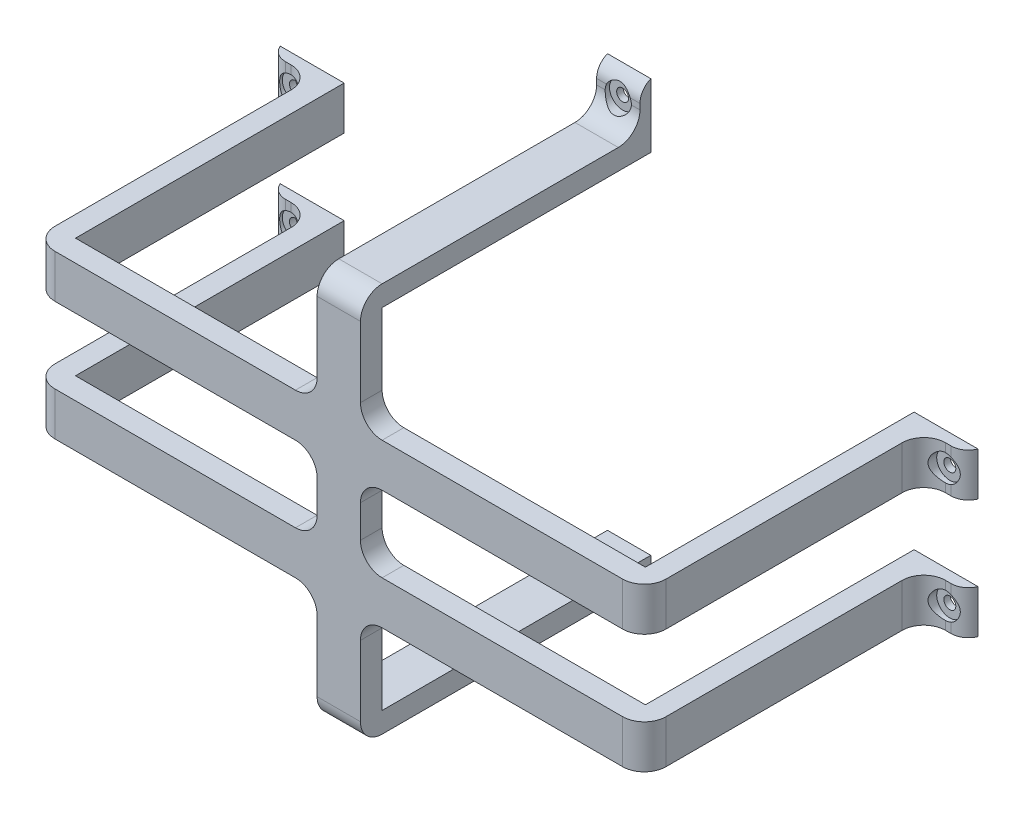
SolidWorks part; units mm, degrees
ref_plane "Front Plane" through (0, 0, 0) normal (0, 0, 1) x (1, 0, 0)
ref_plane "Top Plane" through (0, 0, 0) normal (0, 1, 0) x (1, 0, 0)
ref_plane "Right Plane" through (0, 0, 0) normal (1, 0, 0) x (0, 0, -1)
sketch "Sketch1" plane through (0, 0, 0) normal (0, 0, 1) x (1, 0, 0)
  line L0 (-256.0299, 114.9201) -> (-236.0299, 114.9201)
  line L1 (-236.0299, 114.9201) -> (-236.0299, 62.4201)
  line L2 (-236.0299, 62.4201) -> (-105.0299, 62.4201)
  line L3 (-105.0299, 62.4201) -> (-105.0299, 42.4201)
  line L4 (-105.0299, 42.4201) -> (-236.0299, 42.4201)
  line L5 (-236.0299, 42.4201) -> (-236.0299, 7.4201)
  line L6 (-236.0299, 7.4201) -> (-105.0299, 7.4201)
  line L7 (-105.0299, 7.4201) -> (-105.0299, -12.5799)
  line L8 (-105.0299, -12.5799) -> (-236.0299, -12.5799)
  line L9 (-236.0299, -12.5799) -> (-236.0299, -65.0799)
  line L10 (-236.0299, -65.0799) -> (-256.0299, -65.0799)
  line L11 (-256.0299, -65.0799) -> (-256.0299, -12.5799)
  line L12 (-256.0299, -12.5799) -> (-387.0299, -12.5799)
  line L13 (-387.0299, -12.5799) -> (-387.0299, 7.4201)
  line L14 (-387.0299, 7.4201) -> (-256.0299, 7.4201)
  line L15 (-256.0299, 7.4201) -> (-256.0299, 42.4201)
  line L16 (-256.0299, 42.4201) -> (-387.0299, 42.4201)
  line L17 (-387.0299, 42.4201) -> (-387.0299, 62.4201)
  line L18 (-387.0299, 62.4201) -> (-256.0299, 62.4201)
  line L19 (-256.0299, 62.4201) -> (-256.0299, 114.9201)
  line L20 (-115.0299, -55.0799) -> (-115.0299, 104.9201) construction
  line L21 (-122.0299, -55.0799) -> (-370.0299, -55.0799) construction
  line L22 (-370.0299, 104.9201) -> (-122.0299, 104.9201) construction
  line L23 (-377.0299, 104.9201) -> (-377.0299, -55.0799) construction
  dimension "D1" = 20
  dimension "D2" = 20
  dimension "D3" = 20
  dimension "D4" = 20
  dimension "D5" = 20
  dimension "D6" = 10
  dimension "D7" = 10
  dimension "D8" = 10
  dimension "D9" = 10
  dimension "D10" = 10
  dimension "D11" = 10
  dimension "D12" = 35
extrude "Boss-Extrude1" add sketch "Sketch1" along normal blind 10
sketch "Sketch4" plane through (0, 0, 0) normal (0, 0, -1) x (-1, 0, 0)
  line L0 (236.0299, -65.0799) -> (236.0299, -12.5799) construction
  line L1 (256.0299, -65.0799) -> (236.0299, -65.0799)
  line L2 (256.0299, -65.0799) -> (256.0299, -55.5799)
  line L3 (256.0299, -55.5799) -> (236.0299, -55.5799)
  line L4 (236.0299, -65.0799) -> (236.0299, -55.5799)
  line L5 (105.0299, 7.4201) -> (236.0299, 7.4201) construction
  line L6 (105.0299, -12.5799) -> (114.5299, -12.5799)
  line L7 (105.0299, -12.5799) -> (105.0299, 7.4201)
  line L8 (105.0299, 7.4201) -> (114.5299, 7.4201)
  line L9 (114.5299, -12.5799) -> (114.5299, 7.4201)
  line L10 (105.0299, 62.4201) -> (236.0299, 62.4201) construction
  line L11 (105.0299, 42.4201) -> (114.5299, 42.4201)
  line L12 (105.0299, 42.4201) -> (105.0299, 62.4201)
  line L13 (105.0299, 62.4201) -> (114.5299, 62.4201)
  line L14 (114.5299, 42.4201) -> (114.5299, 62.4201)
  line L15 (236.0299, 62.4201) -> (236.0299, 114.9201) construction
  line L16 (256.0299, 114.9201) -> (236.0299, 114.9201)
  line L17 (256.0299, 114.9201) -> (256.0299, 105.4201)
  line L18 (256.0299, 105.4201) -> (236.0299, 105.4201)
  line L19 (236.0299, 114.9201) -> (236.0299, 105.4201)
  line L20 (256.0299, 62.4201) -> (387.0299, 62.4201) construction
  line L21 (387.0299, 42.4201) -> (377.5299, 42.4201)
  line L22 (387.0299, 42.4201) -> (387.0299, 62.4201)
  line L23 (387.0299, 62.4201) -> (377.5299, 62.4201)
  line L24 (377.5299, 42.4201) -> (377.5299, 62.4201)
  line L25 (256.0299, 7.4201) -> (387.0299, 7.4201) construction
  line L26 (387.0299, -12.5799) -> (377.5299, -12.5799)
  line L27 (387.0299, -12.5799) -> (387.0299, 7.4201)
  line L28 (387.0299, 7.4201) -> (377.5299, 7.4201)
  line L29 (377.5299, -12.5799) -> (377.5299, 7.4201)
  dimension "D1" = 9.5
  dimension "D2" = 9.5
  dimension "D3" = 9.5
  dimension "D4" = 9.5
  dimension "D5" = 9.5
  dimension "D6" = 9.5
extrude "Boss-Extrude2" add sketch "Sketch4" along normal up to surface (123.9883 mm away)
sketch "Sketch6" plane through (0, 0, -123.9883) normal (0, 0, -1) x (-1, 0, 0)
  line L1 (105.0299, -12.5799) -> (85.0299, -12.5799)
  line L2 (105.0299, -12.5799) -> (105.0299, 7.4201)
  line L3 (105.0299, 7.4201) -> (85.0299, 7.4201)
  line L4 (85.0299, -12.5799) -> (85.0299, 7.4201)
  line L5 (105.0299, 42.4201) -> (85.0299, 42.4201)
  line L6 (105.0299, 42.4201) -> (105.0299, 62.4201)
  line L7 (105.0299, 62.4201) -> (85.0299, 62.4201)
  line L8 (85.0299, 42.4201) -> (85.0299, 62.4201)
  line L9 (256.0299, 114.9201) -> (236.0299, 114.9201)
  line L10 (256.0299, 114.9201) -> (256.0299, 134.9201)
  line L11 (256.0299, 134.9201) -> (236.0299, 134.9201)
  line L12 (236.0299, 114.9201) -> (236.0299, 134.9201)
  line L13 (387.0299, 62.4201) -> (407.0299, 62.4201)
  line L14 (387.0299, 62.4201) -> (387.0299, 42.4201)
  line L15 (387.0299, 42.4201) -> (407.0299, 42.4201)
  line L16 (407.0299, 62.4201) -> (407.0299, 42.4201)
  line L17 (387.0299, 7.4201) -> (407.0299, 7.4201)
  line L18 (387.0299, 7.4201) -> (387.0299, -12.5799)
  line L19 (387.0299, -12.5799) -> (407.0299, -12.5799)
  line L20 (407.0299, 7.4201) -> (407.0299, -12.5799)
  line L21 (256.0299, -65.0799) -> (236.0299, -65.0799)
  line L22 (256.0299, -65.0799) -> (256.0299, -85.0799)
  line L23 (256.0299, -85.0799) -> (236.0299, -85.0799)
  line L24 (236.0299, -65.0799) -> (236.0299, -85.0799)
  dimension "D1" = 20
  dimension "D2" = 20
  dimension "D3" = 20
  dimension "D4" = 20
  dimension "D5" = 20
  dimension "D6" = 20
  dimension "D7" = 20
  dimension "D8" = 20
  dimension "D9" = 20
  dimension "D10" = 20
  dimension "D11" = 20
  dimension "D12" = 20
extrude "Boss-Extrude3" add sketch "Sketch6" against normal blind 5
fillet "Fillet1" radius 10 6 edges at (-246.0299, -65.0799, -118.9883) (-387.0299, -2.5799, -118.9883) (-387.0299, 52.4201, -118.9883) (-105.0299, -2.5799, -118.9883) (-105.0299, 52.4201, -118.9883) (-246.0299, 114.9201, -118.9883)
sketch "Sketch7" plane through (0, 0, -118.9883) normal (0, 0, 1) x (1, 0, 0)
  line L0 (-256.0299, 134.9201) -> (-236.0299, 134.9201) construction
  line L1 (-407.0299, 42.4201) -> (-407.0299, 62.4201) construction
  line L2 (-95.0299, 62.4201) -> (-85.0299, 62.4201) construction
  line L3 (-85.0299, 62.4201) -> (-85.0299, 42.4201) construction
  line L4 (-236.0299, -85.0799) -> (-256.0299, -85.0799) construction
  line L5 (-95.0299, 7.4201) -> (-85.0299, 7.4201) construction
  line L7 (-256.0299, -85.0799) -> (-256.0299, -75.0799) construction
  circle A0 centre (-246.0299, 124.9201) radius 6.05
  circle A1 centre (-95.0299, 52.4201) radius 6.05
  circle A2 centre (-95.0299, -2.5799) radius 6.05
  circle A3 centre (-246.0299, -75.0799) radius 6.05
  circle A4 centre (-397.0299, -2.5799) radius 6.05
  circle A5 centre (-397.0299, 52.4201) radius 6.05
  point P14 (0, 0)
  point P15 (0, 0)
  point P20 (0, 0)
  point P21 (0, 0)
  point P22 (0, 0)
  point P23 (0, 0)
  point P26 (0, 0)
  point P31 (0, 0)
  dimension "D1" = 12.1
  dimension "D2" = 10
  dimension "D3" = 10
  dimension "D4" = 10
  dimension "D5" = 10
  dimension "D6" = 10
  dimension "D7" = 10
  dimension "D8" = 10
extrude "Cut-Extrude1" cut sketch "Sketch7" against normal mid plane 4
sketch "Sketch8" plane through (0, 0, -120.9883) normal (0, 0, 1) x (1, 0, 0)
  circle A0 centre (-246.0299, -75.0799) radius 2.75
  circle A1 centre (-397.0299, -2.5799) radius 2.75
  circle A2 centre (-397.0299, 52.4201) radius 2.75
  circle A3 centre (-246.0299, 124.9201) radius 2.75
  circle A4 centre (-95.0299, 52.4201) radius 2.75
  circle A5 centre (-95.0299, -2.5799) radius 2.75
  dimension "D1" = 5.5
extrude "Cut-Extrude2" cut sketch "Sketch8" against normal through all
fillet "Fillet2" radius 10 6 edges at (-246.0299, -65.0799, 10) (-105.0299, -2.5799, 10) (-105.0299, 52.4201, 10) (-246.0299, 114.9201, 10) (-387.0299, 52.4201, 10) (-387.0299, -2.5799, 10)
fillet "Fillet3" radius 10 8 edges at (-256.0299, 62.4201, 5) (-236.0299, 62.4201, 5) (-236.0299, 7.4201, 5) (-256.0299, 7.4201, 5) (-256.0299, 42.4201, 5) (-236.0299, 42.4201, 5) (-236.0299, -12.5799, 5) (-256.0299, -12.5799, 5)
fillet "Fillet4" radius 8 6 edges at (-246.0299, 134.9201, -118.9883) (-407.0299, 52.4201, -118.9883) (-407.0299, -2.5799, -118.9883) (-246.0299, -85.0799, -118.9883) (-85.0299, -2.5799, -118.9883) (-85.0299, 52.4201, -118.9883)
